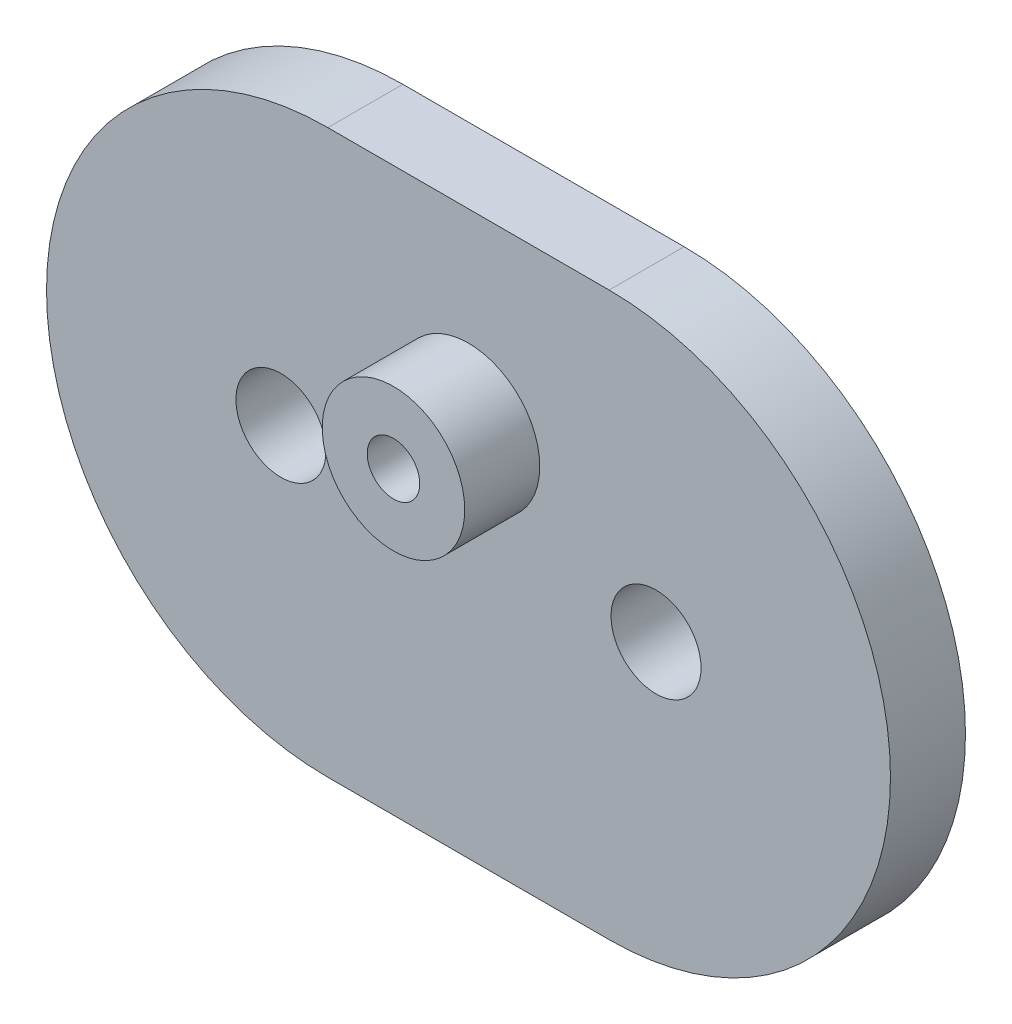
SolidWorks part; units mm, degrees
ref_plane "前视基准面" through (0, 0, 0) normal (0, 0, 1) x (1, 0, 0)
ref_plane "上视基准面" through (0, 0, 0) normal (0, 1, 0) x (1, 0, 0)
ref_plane "右视基准面" through (0, 0, 0) normal (1, 0, 0) x (0, 0, -1)
sketch "草图1" plane through (0, 0, 0) normal (0, 0, 1) x (1, 0, 0)
  line L0 (-7.5, 0) -> (7.5, 0) construction
  line L1 (-7.5, 15) -> (7.5, 15)
  line L2 (-7.5, -15) -> (7.5, -15)
  arc A0 (-7.5, 15) -> (-7.5, -15) centre (-7.5, 0) ccw
  arc A1 (7.5, -15) -> (7.5, 15) centre (7.5, 0) ccw
  circle A2 centre (0, 5) radius 1.4
  circle A3 centre (-10, 0) radius 2.4
  circle A4 centre (10, 0) radius 2.4
  circle A5 centre (0, 5) radius 3.8
  point P3 (0, 0)
  dimension "D1" = 15
  dimension "D3" = 2.8
  dimension "D4" = 5
  dimension "D5" = 4.8
  dimension "D6" = 10
  dimension "D7" = 10
  dimension "D2" = 15
extrude "凸台-拉伸1" add sketch "草图1" along normal blind 4 contours L2 A1 L1 A0 A5 A4 A3 region at (0, -0.2109, 0)
extrude "凸台-拉伸2" add sketch "草图1<3>" along normal blind 8 contours A5 A2 region at (-3.6925, 5, 0)
sketch "草图1<3>" plane through (0, 0, 0) normal (0, 0, 1) x (1, 0, 0) same geometry as "草图1"
